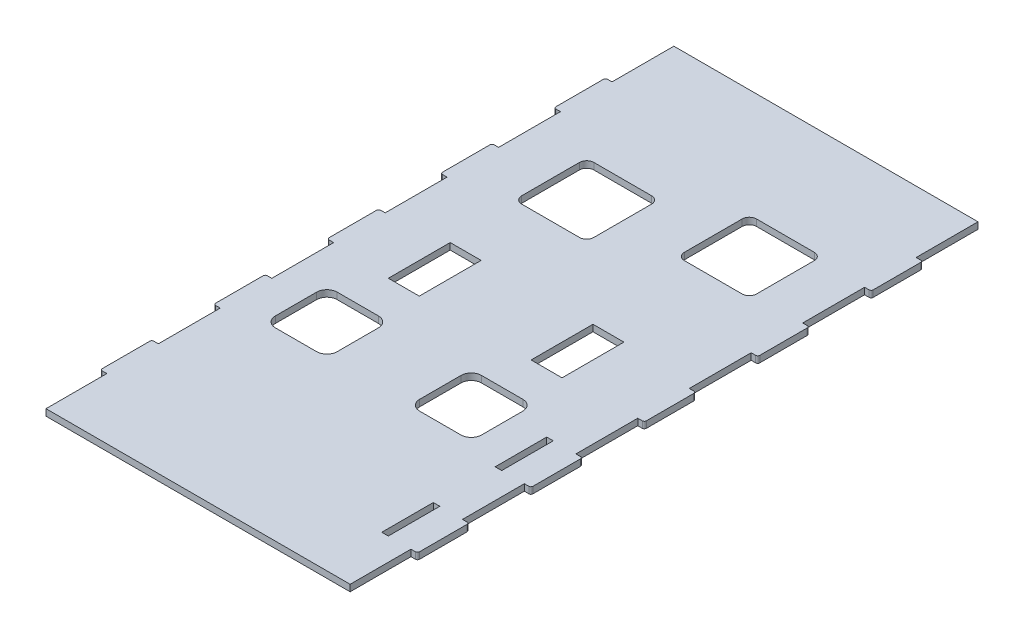
SolidWorks part; units mm, degrees
material "Beech"
ref_plane "Front Plane" through (0, 0, 0) normal (0, 0, 1) x (1, 0, 0)
ref_plane "Top Plane" through (0, 0, 0) normal (0, 1, 0) x (1, 0, 0)
ref_plane "Right Plane" through (0, 0, 0) normal (1, 0, 0) x (0, 0, -1)
sketch "Sketch1" plane through (0, 0, 0) normal (0, 1, 0) x (1, 0, 0)
  line L1 (0, 0) -> (295, 0)
  line L2 (0, 0) -> (0, 59)
  line L3 (0, 609) -> (295, 609)
  line L4 (295, 0) -> (295, 59)
  line L5 (0, 59) -> (-6.35, 59)
  line L7 (0, 109) -> (-6.35, 109)
  line L8 (-6.35, 59) -> (-6.35, 109)
  line L9 (0, 169) -> (-6.35, 169)
  line L10 (-6.35, 169) -> (-6.35, 219)
  line L11 (0, 219) -> (-6.35, 219)
  line L13 (0, 279) -> (-6.35, 279)
  line L14 (-6.35, 279) -> (-6.35, 329)
  line L15 (0, 329) -> (-6.35, 329)
  line L17 (0, 389) -> (-6.35, 389)
  line L18 (-6.35, 389) -> (-6.35, 439)
  line L19 (0, 439) -> (-6.35, 439)
  line L21 (0, 499) -> (-6.35, 499)
  line L22 (-6.35, 499) -> (-6.35, 549)
  line L23 (0, 549) -> (-6.35, 549)
  line L25 (295, 59) -> (301.35, 59)
  line L27 (295, 109) -> (301.35, 109)
  line L28 (301.35, 59) -> (301.35, 109)
  line L29 (295, 169) -> (301.35, 169)
  line L30 (301.35, 169) -> (301.35, 219)
  line L31 (295, 219) -> (301.35, 219)
  line L33 (295, 279) -> (301.35, 279)
  line L34 (301.35, 279) -> (301.35, 329)
  line L35 (295, 329) -> (301.35, 329)
  line L37 (295, 389) -> (301.35, 389)
  line L38 (301.35, 389) -> (301.35, 439)
  line L39 (295, 439) -> (301.35, 439)
  line L41 (295, 499) -> (301.35, 499)
  line L42 (301.35, 499) -> (301.35, 549)
  line L43 (295, 549) -> (301.35, 549)
  line L44 (0, 549) -> (0, 609)
  line L46 (0, 329) -> (0, 389)
  line L49 (0, 219) -> (0, 279)
  line L50 (0, 109) -> (0, 169)
  line L51 (295, 109) -> (295, 169)
  line L52 (295, 219) -> (295, 279)
  line L53 (295, 329) -> (295, 389)
  line L54 (295, 439) -> (295, 499)
  line L55 (295, 549) -> (295, 609)
  line L56 (0, 439) -> (0, 499)
  dimension "D1" = 609
  dimension "D2" = 295
  dimension "D3" = 6.35
  dimension "D4" = 50
  dimension "D5" = 59
  dimension "D7" = 60
  dimension "D8" = 50
  dimension "D9" = 6.35
  dimension "D11" = 59
  dimension "D12" = 60
  dimension "D6" = 5
  dimension "D10" = 5
extrude "Boss-Extrude1" add sketch "Sketch1" along normal blind 6.35
fillet "Fillet1" radius 2 20 edges at (301.35, 3.175, -549) (301.35, 3.175, -499) (301.35, 3.175, -439) (301.35, 3.175, -389) (301.35, 3.175, -329) (301.35, 3.175, -279) (301.35, 3.175, -219) (301.35, 3.175, -169) (301.35, 3.175, -109) (301.35, 3.175, -59) (-6.35, 3.175, -59) (-6.35, 3.175, -109) (-6.35, 3.175, -169) (-6.35, 3.175, -219) (-6.35, 3.175, -279) (-6.35, 3.175, -329) (-6.35, 3.175, -389) (-6.35, 3.175, -439) (-6.35, 3.175, -499) (-6.35, 3.175, -549)
sketch "Sketch2" plane through (0, 6.35, 0) normal (0, 1, 0) x (1, 0, 0)
  line L0 (266.65, 0) -> (266.65, 100) construction
  line L1 (0, 0) -> (295, 0) construction
  line L2 (0, 609) -> (0, 0) construction
  line L3 (295, 609) -> (295, 0) construction
  line L4 (0, 150) -> (266.65, 100) construction
  line L5 (266.65, 169) -> (266.65, 219)
  line L6 (266.65, 59) -> (273, 59)
  line L7 (266.65, 59) -> (266.65, 109)
  line L8 (266.65, 109) -> (273, 109)
  line L9 (273, 59) -> (273, 109)
  line L10 (266.65, 169) -> (273, 169)
  line L11 (273, 169) -> (273, 219)
  line L12 (266.65, 219) -> (273, 219)
  line L13 (0, 84.2124) -> (266.65, 84) construction
  line L14 (58.849, 472.5538) -> (114.849, 472.5538)
  line L15 (51.849, 465.5538) -> (51.849, 409.5538)
  line L16 (58.849, 402.5538) -> (114.849, 402.5538)
  line L17 (121.849, 465.5538) -> (121.849, 409.5538)
  line L18 (185.2335, 503.9695) -> (241.2335, 503.9695)
  line L19 (178.2335, 496.9695) -> (178.2335, 440.9695)
  line L20 (185.2335, 433.9695) -> (241.2335, 433.9695)
  line L21 (248.2335, 496.9695) -> (248.2335, 440.9695)
  line L22 (43.325, 239.1432) -> (83.325, 239.1432)
  line L23 (33.325, 229.1432) -> (33.325, 189.1432)
  line L24 (43.325, 179.1432) -> (83.325, 179.1432)
  line L25 (93.325, 229.1432) -> (93.325, 189.1432)
  line L26 (33.325, 239.1432) -> (93.325, 179.1432) construction
  line L27 (33.325, 179.1432) -> (93.325, 239.1432) construction
  line L32 (133.325, 0) -> (133.325, 609) construction
  line L33 (295, 609) -> (0, 609) construction
  line L34 (56.474, 335.5741) -> (86.474, 335.5741)
  line L35 (56.474, 335.5741) -> (56.474, 275.5741)
  line L36 (56.474, 275.5741) -> (86.474, 275.5741)
  line L37 (86.474, 335.5741) -> (86.474, 275.5741)
  line L38 (194.3557, 336.1934) -> (224.3557, 336.1934)
  line L39 (194.3557, 336.1934) -> (194.3557, 276.1934)
  line L40 (194.3557, 276.1934) -> (224.3557, 276.1934)
  line L41 (224.3557, 336.1934) -> (224.3557, 276.1934)
  line L42 (233.325, 179.1432) -> (173.325, 239.1432) construction
  line L43 (233.325, 239.1432) -> (173.325, 179.1432) construction
  line L44 (173.325, 229.1432) -> (173.325, 189.1432)
  line L45 (223.325, 179.1432) -> (183.325, 179.1432)
  line L46 (233.325, 229.1432) -> (233.325, 189.1432)
  line L47 (223.325, 239.1432) -> (183.325, 239.1432)
  arc A0 (51.849, 409.5538) -> (58.849, 402.5538) centre (58.849, 409.5538) ccw
  arc A1 (114.849, 402.5538) -> (121.849, 409.5538) centre (114.849, 409.5538) ccw
  arc A2 (114.849, 472.5538) -> (121.849, 465.5538) centre (114.849, 465.5538) cw
  arc A3 (58.849, 472.5538) -> (51.849, 465.5538) centre (58.849, 465.5538) ccw
  arc A4 (178.2335, 440.9695) -> (185.2335, 433.9695) centre (185.2335, 440.9695) ccw
  arc A5 (241.2335, 433.9695) -> (248.2335, 440.9695) centre (241.2335, 440.9695) ccw
  arc A6 (241.2335, 503.9695) -> (248.2335, 496.9695) centre (241.2335, 496.9695) cw
  arc A7 (185.2335, 503.9695) -> (178.2335, 496.9695) centre (185.2335, 496.9695) ccw
  arc A8 (33.325, 189.1432) -> (43.325, 179.1432) centre (43.325, 189.1432) ccw
  arc A9 (83.325, 179.1432) -> (93.325, 189.1432) centre (83.325, 189.1432) ccw
  arc A10 (83.325, 239.1432) -> (93.325, 229.1432) centre (83.325, 229.1432) cw
  arc A11 (43.325, 239.1432) -> (33.325, 229.1432) centre (43.325, 229.1432) ccw
  arc A16 (223.325, 239.1432) -> (233.325, 229.1432) centre (223.325, 229.1432) cw
  arc A17 (183.325, 239.1432) -> (173.325, 229.1432) centre (183.325, 229.1432) ccw
  arc A18 (183.325, 179.1432) -> (173.325, 189.1432) centre (183.325, 189.1432) cw
  arc A19 (233.325, 189.1432) -> (223.325, 179.1432) centre (223.325, 189.1432) cw
  point P33 (121.849, 402.5538)
  point P36 (121.849, 472.5538)
  point P39 (51.849, 472.5538)
  point P42 (178.2335, 433.9695)
  point P47 (248.2335, 503.9695)
  point P50 (178.2335, 503.9695)
  point P51 (63.325, 209.1432)
  point P74 (133.325, 84.1062)
  point P99 (203.325, 209.1432)
  dimension "D10" = 7
  dimension "D11" = 7
  dimension "D16" = 10
  dimension "D17" = 70
  dimension "D1" = 100
  dimension "D2" = 150
  dimension "D3" = 6.35
  dimension "D4" = 50
  dimension "D6" = 70
  dimension "D7" = 70
  dimension "D8" = 70
  dimension "D9" = 70
  dimension "D12" = 60
  dimension "D13" = 60
  dimension "D14" = 22
  dimension "D15" = 59
  dimension "D18" = 30
  dimension "D19" = 60
  dimension "D20" = 30
  dimension "D21" = 60
  dimension "D5" = 2
extrude "Cut-Extrude1" cut sketch "Sketch2" against normal blind 6.35
